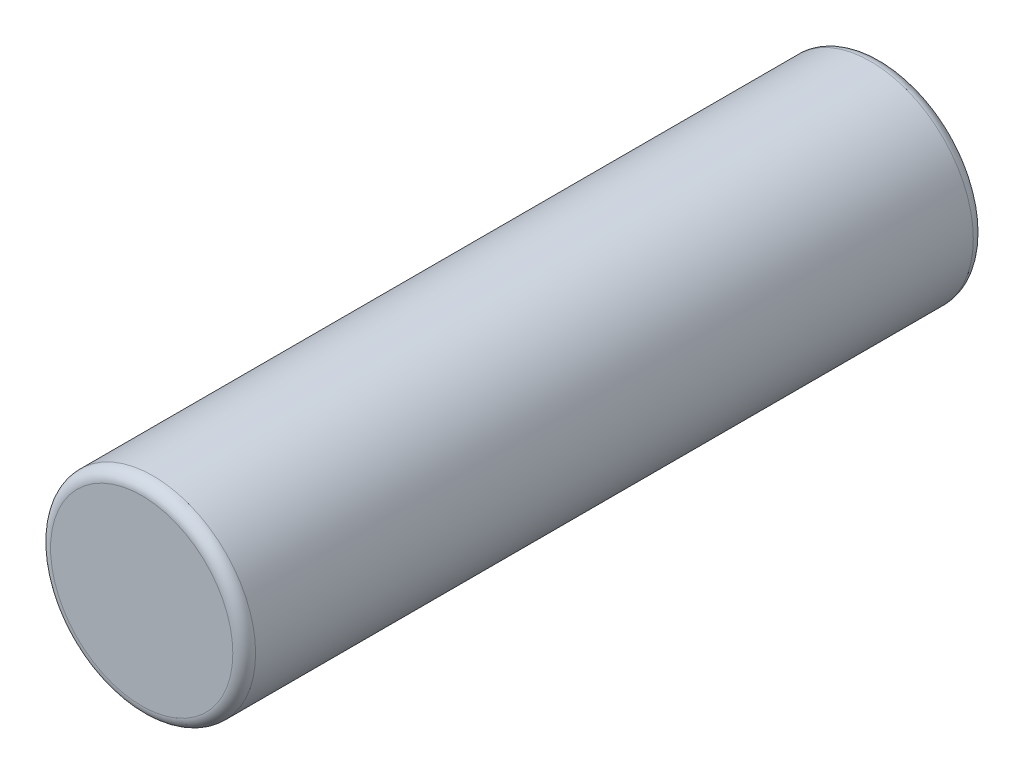
SolidWorks part; units mm, degrees
ref_plane "Спереди" through (0, 0, 0) normal (0, 0, 1) x (1, 0, 0)
ref_plane "Сверху" through (0, 0, 0) normal (0, 1, 0) x (1, 0, 0)
ref_plane "Справа" through (0, 0, 0) normal (1, 0, 0) x (0, 0, -1)
sketch "Эскиз1" plane through (0, 0, 0) normal (0, 0, 1) x (1, 0, 0)
  circle A0 centre (0, 0) radius 9
  dimension "D1" = 18
extrude "Бобышка-Вытянуть1" add sketch "Эскиз1" along normal blind 65
fillet "Скругление1" radius 1 2 edges at (9, 0, 65) (9, 0, 0)
